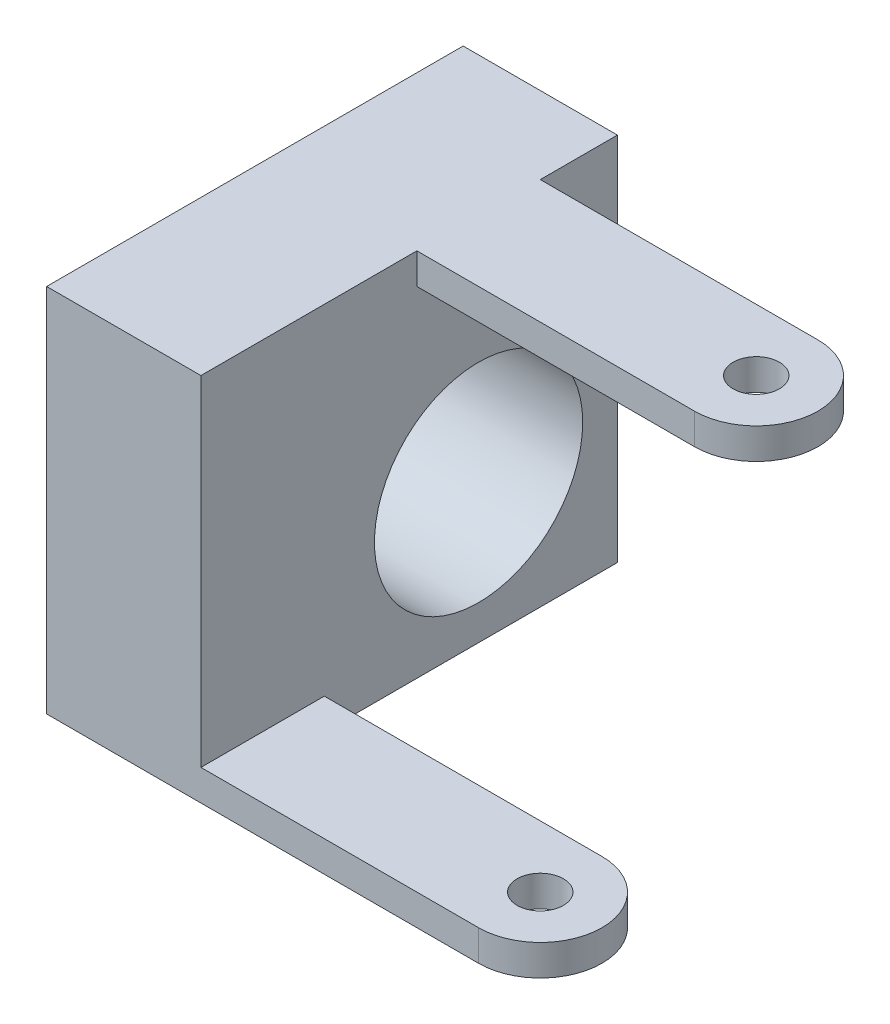
SolidWorks part; units mm, degrees
ref_plane "Front Plane" through (0, 0, 0) normal (0, 0, 1) x (1, 0, 0)
ref_plane "Top Plane" through (0, 0, 0) normal (0, 1, 0) x (1, 0, 0)
ref_plane "Right Plane" through (0, 0, 0) normal (1, 0, 0) x (0, 0, -1)
sketch "Sketch2" plane through (0, 0, 0) normal (0, 1, 0) x (1, 0, 0)
  line L0 (-5, -4.5) -> (5, -4.5) construction
  line L1 (-5, -18) -> (5, -18)
  line L2 (-5, -18) -> (-5, 9)
  line L3 (-5, 9) -> (5, 9)
  line L4 (5, -18) -> (5, 9)
  line L5 (0, 9) -> (0, -18) construction
  point P0 (0, 0)
  dimension "D3" = 9
  dimension "D1" = 10
  dimension "D2" = 18
extrude "Boss-Extrude1" add sketch "Sketch2" along normal blind 24
sketch "Sketch3" plane through (5, 0, 0) normal (1, 0, 0) x (0, 0, -1)
  line L0 (-18, 9) -> (9, 9) construction
  line L3 (-18, 0) -> (9, 0) construction
  line L4 (-18, 24) -> (-18, 0) construction
  line L5 (9, 24) -> (9, 0) construction
  circle A0 centre (0, 9) radius 6.75
  dimension "D1" = 13.5
  dimension "D2" = 9
extrude "Cut-Extrude1" cut sketch "Sketch3" against normal up to surface (10 mm away) up to face at (-5, 12, 4.5)
sketch "Sketch6" plane through (5, 0, 0) normal (1, 0, 0) x (0, 0, -1)
  line L0 (-18, 24) -> (9, 24) construction
  line L1 (-4, 24) -> (4, 24)
  line L2 (-4, 24) -> (-4, 22)
  line L3 (-4, 22) -> (4, 22)
  line L4 (4, 24) -> (4, 22)
  line L5 (0, 24) -> (0, 0) construction
  dimension "D1" = 8
  dimension "D2" = 2
extrude "Boss-Extrude2" add sketch "Sketch6" along normal blind 22
fillet "Fillet1" 2 edges at (27, 23, 4) (27, 23, -4) type full round first side face at (16, 23, 4) second side face at (16, 23, -4) middle face at (27, 23, 0)
sketch "Sketch8" plane through (0, 24, 0) normal (0, 1, 0) x (1, 0, 0)
  circle A0 centre (23, 0) radius 1.5
  point P9 (0, 0)
  dimension "D1" = 3
extrude "Cut-Extrude2" cut sketch "Sketch8" against normal up to surface (2 mm away) up to face at (15, 22, 0)
sketch "Sketch10" plane through (5, 0, 0) normal (1, 0, 0) x (0, 0, -1)
  line L1 (-18, 0) -> (-10, 0)
  line L2 (-18, 0) -> (-18, 2)
  line L3 (-18, 2) -> (-10, 2)
  line L4 (-10, 0) -> (-10, 2)
  dimension "D1" = 2
  dimension "D2" = 8
extrude "Boss-Extrude3" add sketch "Sketch10" along normal blind 22
fillet "Fillet2" 2 edges at (27, 1, 18) (27, 1, 10) type full round first side face at (9, 8.6667, 18) second side face at (16, 1, 10) middle face at (27, 1, 14)
sketch "Sketch11" plane through (0, 2, 0) normal (0, 1, 0) x (1, 0, 0)
  circle A0 centre (23, -14) radius 1.5
  dimension "D1" = 3
extrude "Cut-Extrude3" cut sketch "Sketch11" against normal up to surface (2 mm away) up to face at (8.3333, 0, 6.3333)
